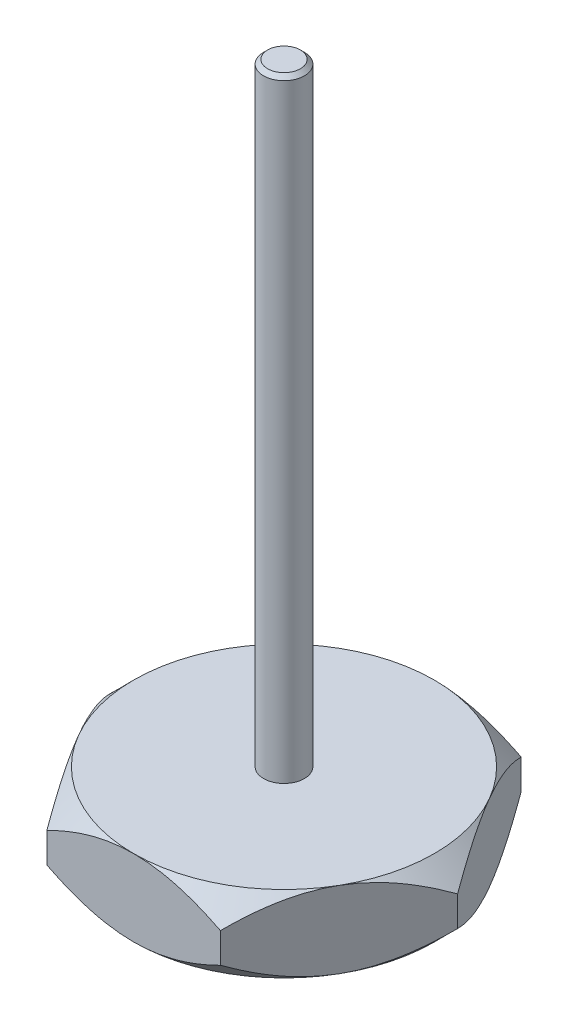
SolidWorks part; units mm, degrees
material "Plain Carbon Steel"
ref_plane "Front Plane" through (0, 0, 0) normal (0, 0, 1) x (1, 0, 0)
ref_plane "Top Plane" through (0, 0, 0) normal (0, 1, 0) x (1, 0, 0)
ref_plane "Right Plane" through (0, 0, 0) normal (1, 0, 0) x (0, 0, -1)
sketch "Sketch1" plane through (0, 0, 0) normal (0, 1, 0) x (1, 0, 0)
  line L1 (-4.25, -7.3612) -> (4.25, -7.3612)
  line L2 (4.25, -7.3612) -> (8.5, 0)
  line L3 (8.5, 0) -> (4.25, 7.3612)
  line L4 (4.25, 7.3612) -> (-4.25, 7.3612)
  line L5 (-4.25, 7.3612) -> (-8.5, 0)
  line L6 (-8.5, 0) -> (-4.25, -7.3612)
  circle A0 centre (0, 0) radius 7.3612 construction
  circle A1 centre (0, 0) radius 1
  dimension "D2" = 2
  dimension "D1" = 17
extrude "Boss-Extrude1" add sketch "Sketch1" along normal blind 3.75 contours L1 L2 L3 L4 L5 L6
extrude "Boss-Extrude2" add sketch "Sketch1<3>" along normal blind 33.75 contours A1
sketch "Sketch1<3>" plane through (0, 0, 0) normal (0, 1, 0) x (1, 0, 0) same geometry as "Sketch1"
sketch "Sketch2" plane through (0, 0, 0) normal (0, -1, 0) x (1, 0, 0)
  line L0 (-8.5, 0) -> (-4.25, 7.3612) construction
  circle A0 centre (0, 0) radius 7.3612
extrude "Cut-Extrude5" cut sketch "Sketch2" against normal through all draft 45 flip side to cut
chamfer "Chamfer1" distance 0.2 angle 45 1 edges at (0, 33.75, 1)
sketch "Sketch3" plane through (0, 3.75, 0) normal (0, 1, 0) x (1, 0, 0)
  line L0 (-4.25, 7.3612) -> (-8.5, 0) construction
  circle A0 centre (0, 0) radius 7.3612
extrude "Cut-Extrude6" cut sketch "Sketch3" against normal through all draft 45 flip side to cut
